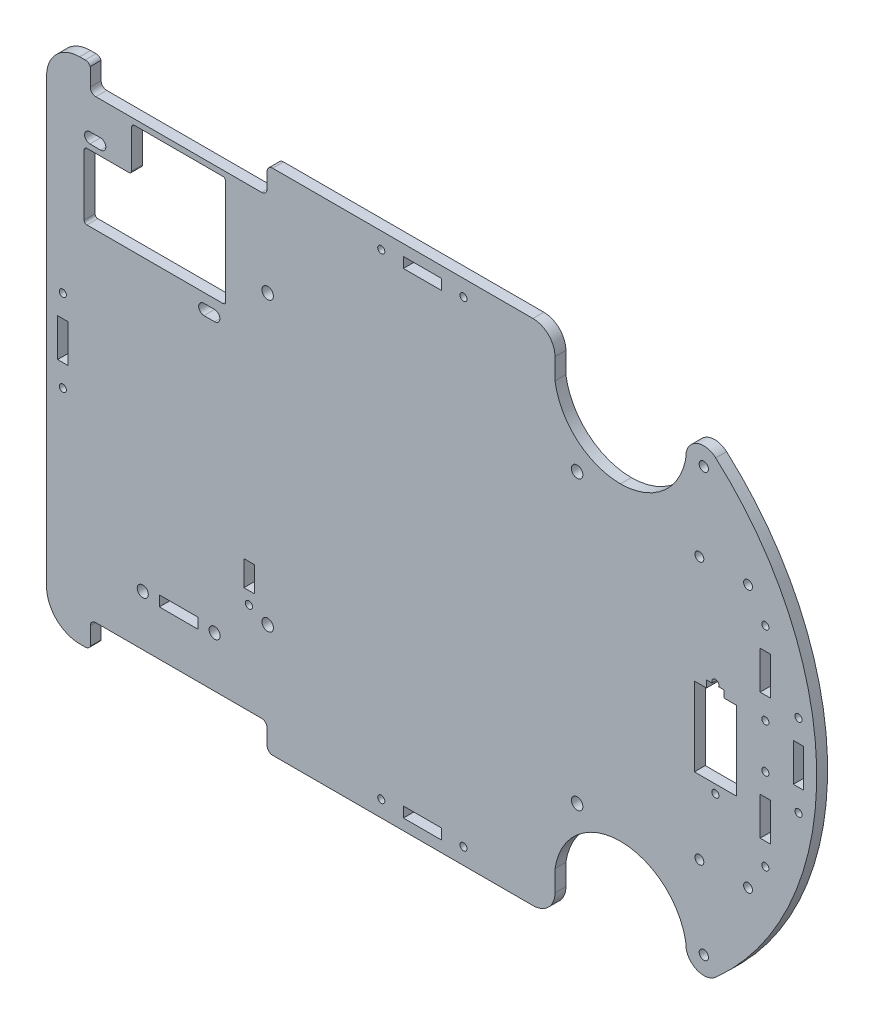
SolidWorks part; units mm, degrees
ref_plane "Alzado" through (0, 0, 0) normal (0, 0, 1) x (1, 0, 0)
ref_plane "Planta" through (0, 0, 0) normal (0, 1, 0) x (1, 0, 0)
ref_plane "Vista lateral" through (0, 0, 0) normal (1, 0, 0) x (0, 0, -1)
sketch "Croquis1" plane through (0, 0, 0) normal (0, 0, 1) x (1, 0, 0)
  line L1 (-107.95, -73.025) -> (107.95, -73.025)
  line L2 (-107.95, -73.025) -> (-107.95, 73.025)
  line L3 (-107.95, 73.025) -> (107.95, 73.025)
  line L4 (107.95, -73.025) -> (107.95, 73.025)
  line L5 (-107.95, -73.025) -> (107.95, 73.025) construction
  line L6 (-107.95, 73.025) -> (107.95, -73.025) construction
  point P0 (0, 0)
  dimension "D1" = 146.05
  dimension "D2" = 215.9
extrude "BI" add sketch "Croquis1" along normal blind 3.1242
sketch "Croquis2" plane through (0, 0, 3.1242) normal (0, 0, 1) x (1, 0, 0)
  line L0 (-107.95, -73.025) -> (107.95, -73.025) construction
  line L1 (107.95, 73.025) -> (43.634, 73.025)
  line L2 (107.95, 73.025) -> (107.95, -73.025)
  line L3 (107.95, -73.025) -> (43.634, -73.025)
  line L4 (43.634, 73.025) -> (43.634, -73.025)
  line L5 (0, 0) -> (107.95, 0) construction
  line L6 (71.3851, 73.025) -> (80.1989, 73.025)
  line L7 (71.3851, 73.025) -> (71.3851, 55.6514)
  line L8 (71.3851, 55.6514) -> (80.1989, 55.6514)
  line L9 (80.1989, 73.025) -> (80.1989, 55.6514)
  line L10 (80.1989, -73.025) -> (80.1989, -55.6514)
  line L11 (71.3851, -55.6514) -> (80.1989, -55.6514)
  line L12 (71.3851, -73.025) -> (71.3851, -55.6514)
  line L13 (71.3851, -73.025) -> (80.1989, -73.025)
  circle A0 centre (80.8339, 60.7314) radius 2.921
  circle A1 centre (80.8339, 60.7314) radius 1.3335
  circle A2 centre (80.8339, -60.7314) radius 1.3335
  circle A3 centre (80.8339, -60.7314) radius 2.921
  point P11 (75.792, 73.025)
  point P12 (75.792, 55.6514)
  point P13 (80.8339, 57.8104)
  point P14 (83.7549, 60.7314)
  point P28 (83.7549, -60.7314)
  point P29 (80.8339, -57.8104)
  point P30 (75.792, -55.6514)
  point P31 (75.792, -73.025)
  point P32 (80.8339, -59.3979)
  point P33 (80.8339, 59.3979)
  point P34 (80.8339, -62.0649)
  point P35 (80.8339, 62.0649)
  dimension "D3" = 5.842
  dimension "D4" = 1.5875
  dimension "D1" = 43.634
  dimension "D2" = 8.8138
  dimension "D5" = 3.556
  dimension "D6" = 17.3736
  dimension "D7" = 118.7958
  dimension "D8" = 118.7958
  dimension "D9" = 124.1298
extrude "Direccion" cut sketch "Croquis2" against normal through all contours L9 A1 | L9 A1 | A2 region at (81.0771, 60.7314, 3.1242) region at (79.9121, 60.7314, 3.1242)
sketch "Croquis9" plane through (0, 0, 3.1242) normal (0, 0, 1) x (1, 0, 0)
  line L0 (68.1339, 37.6809) -> (93.5339, 37.6809) construction
  line L1 (0, 0) -> (107.95, 0) construction
  line L2 (107.95, -73.025) -> (107.95, 73.025) construction
  line L3 (68.1339, -37.6809) -> (93.5339, -37.6809) construction
  circle A0 centre (68.1339, 37.6809) radius 1.27
  circle A1 centre (93.5339, 37.6809) radius 1.27
  circle A2 centre (93.5339, 37.6809) radius 2.794
  circle A3 centre (80.8339, 60.7314) radius 1.3335 construction
  circle A4 centre (80.8339, 60.7314) radius 1.3335
  circle A5 centre (93.5339, -37.6809) radius 1.27
  circle A6 centre (68.1339, -37.6809) radius 1.27
  circle A7 centre (80.8339, 37.6809) radius 1.27
  circle A8 centre (80.8339, -37.6809) radius 1.27
  circle A9 centre (79.5639, 37.6809) radius 1.27
  circle A10 centre (79.5639, -37.6809) radius 1.27
  point P4 (80.8339, 62.0649)
  point P5 (93.5339, 34.8869)
  point P9 (80.8339, 37.6809)
  point P22 (93.5339, -34.8869)
  point P23 (69.4039, 37.6809)
  point P24 (92.2639, 37.6809)
  dimension "D1" = 12.7
  dimension "D2" = 2.54
  dimension "D3" = 27.178
  dimension "D4" = 5.588
  dimension "D5" = 23.0505
  dimension "D6" = 2.667
extrude "Suspension" cut sketch "Croquis9" against normal through all contours A9 | A1 | A10 | A5
sketch "Croquis3" plane through (0, 0, 3.1242) normal (0, 0, 1) x (1, 0, 0)
  line L0 (107.95, -73.025) -> (107.95, 73.025) construction
  line L1 (107.95, 73.025) -> (-107.95, 73.025) construction
  line L2 (0, 0) -> (107.95, 0) construction
  line L3 (38.1, 73.025) -> (75.6745, 73.025)
  line L4 (38.1, 73.025) -> (38.1, 44.45)
  line L5 (38.1, 44.45) -> (75.6745, 44.45)
  line L6 (75.6745, 73.025) -> (75.6745, 44.45)
  line L7 (75.6745, -73.025) -> (75.6745, -44.45)
  line L8 (38.1, -44.45) -> (75.6745, -44.45)
  line L9 (38.1, -73.025) -> (38.1, -44.45)
  line L10 (38.1, -73.025) -> (75.6745, -73.025)
  line L11 (-107.95, -73.025) -> (107.95, -73.025) construction
  line L12 (-98.425, 73.025) -> (0, 73.025)
  line L13 (-107.95, 63.5) -> (-107.95, -63.5)
  line L14 (-98.425, -73.025) -> (0, -73.025)
  line L15 (0, 73.025) -> (0, -73.025)
  circle A0 centre (80.8339, 60.7314) radius 5.1594
  arc A1 (84.8004, 64.0308) -> (84.8004, -64.0308) centre (7.8219, 0) cw
  arc A2 (75.6745, 60.7314) -> (75.5727, 59.7195) centre (70.5945, 60.7314) cw
  arc A3 (31.75, 73.025) -> (38.1, 66.675) centre (31.75, 66.675) cw
  arc A4 (38.0482, 65.8655) -> (56.8873, 44.45) centre (56.8873, 63.4441) ccw
  arc A5 (38.0482, -65.8655) -> (56.8873, -44.45) centre (56.8873, -63.4441) cw
  arc A6 (31.75, -73.025) -> (38.1, -66.675) centre (31.75, -66.675) ccw
  arc A7 (75.5727, -59.7195) -> (56.8873, -44.45) centre (56.8873, -63.5176) ccw
  circle A8 centre (80.8339, -60.7314) radius 5.1594
  arc A9 (-107.95, -63.5) -> (-98.425, -73.025) centre (-98.425, -63.5) ccw
  arc A10 (-98.425, 73.025) -> (-107.95, 63.5) centre (-98.425, 63.5) ccw
  arc A11 (75.5727, 59.7195) -> (56.8873, 44.45) centre (56.8873, 63.5176) cw
  arc A12 (75.6745, -60.7314) -> (75.5727, -59.7195) centre (70.5945, -60.7314) ccw
  point P48 (-107.95, 73.025)
  line M6 (107.95, -73.025) -> (107.95, 73.025)
  line M7 (107.95, 73.025) -> (-107.95, 73.025)
  line M8 (-107.95, 73.025) -> (-107.95, -73.025)
  line M9 (-107.95, -73.025) -> (107.95, -73.025)
  dimension "D1" = 28.575
  dimension "D3" = 6.35
  dimension "D4" = 9.525
  dimension "D5" = 10.3187
  dimension "D6" = 5.08
  dimension "D2" = 38.1
extrude "Forma delantera" cut sketch "Croquis3" against normal through all contours A3 A4 L4 M7 | A11 A2 L6 L4 A4 M7 | A0 A1 L6 M6 M7 | A1 A8 L7 M9 M6 | L7 A12 A7 A5 L9 M9 | A6 L9 A5 M9 | A10 M7 M8 | A9 M8 M9 region at (56.8973, 60.3698, 3.1242) region at (36.6816, 71.6066, 3.1242) region at (97.7834, 56.0016, 3.1242) region at (97.7834, -56.0016, 3.1242) region at (-105.8224, 70.8974, 3.1242) region at (-105.8224, -70.8974, 3.1242) region at (36.6816, -71.6066, 3.1242) region at (56.8973, -60.3698, 3.1242)
sketch "Croquis5" plane through (0, 0, 3.1242) normal (0, 0, 1) x (1, 0, 0)
  line L0 (-98.425, -73.025) -> (31.75, -73.025) construction
  line L1 (-17.0815, -19.2786) -> (33.3375, -19.2786)
  line L2 (-17.0815, -19.2786) -> (-17.0815, -69.85)
  line L3 (-17.0815, -69.85) -> (33.3375, -69.85)
  line L4 (33.3375, -19.2786) -> (33.3375, -69.85)
  line L5 (-17.0815, -44.5643) -> (33.3375, -44.5643) construction
  line L6 (38.1, -66.675) -> (38.1, -60.6489) construction
  line L7 (33.3375, -69.85) -> (25.9715, -69.85)
  line L8 (33.3375, -69.85) -> (33.3375, -19.2786)
  line L9 (33.3375, -19.2786) -> (25.9715, -19.2786)
  line L10 (25.9715, -69.85) -> (25.9715, -19.2786)
  line L11 (-17.0815, -19.2786) -> (-6.9215, -19.2786)
  line L12 (-17.0815, -19.2786) -> (-17.0815, -69.85)
  line L13 (-17.0815, -69.85) -> (-6.9215, -69.85)
  line L14 (-6.9215, -19.2786) -> (-6.9215, -69.85)
  line L15 (25.9715, -33.2486) -> (33.3375, -33.2486)
  line L16 (25.9715, -33.2486) -> (25.9715, -55.88)
  line L17 (25.9715, -55.88) -> (33.3375, -55.88)
  line L18 (33.3375, -33.2486) -> (33.3375, -55.88)
  line L19 (-6.9215, -29.0576) -> (-17.0815, -29.0576)
  line L20 (-6.9215, -29.0576) -> (-6.9215, -60.071)
  line L21 (-6.9215, -60.071) -> (-17.0815, -60.071)
  line L22 (-17.0815, -29.0576) -> (-17.0815, -60.071)
  circle A0 centre (29.7815, -24.7396) radius 1.651
  circle A1 centre (-10.3505, -24.6126) radius 1.651
  circle A2 centre (29.7815, -64.389) radius 1.651
  circle A3 centre (-10.3505, -64.516) radius 1.651
  arc A4 (31.75, -55.88) -> (33.3375, -54.2925) centre (31.75, -54.2925) ccw
  arc A5 (29.6545, -55.88) -> (25.9715, -59.563) centre (29.6545, -59.563) ccw
  arc A6 (-12.0015, -60.071) -> (-17.0815, -54.991) centre (-12.0015, -54.991) cw
  arc A7 (-10.0965, -60.071) -> (-6.9215, -63.246) centre (-10.0965, -63.246) cw
  arc A8 (31.75, -33.2486) -> (33.3375, -34.8361) centre (31.75, -34.8361) cw
  arc A9 (29.6545, -33.2486) -> (25.9715, -29.5656) centre (29.6545, -29.5656) cw
  arc A10 (-12.0015, -29.0576) -> (-17.0815, -34.1376) centre (-12.0015, -34.1376) ccw
  arc A11 (-10.0965, -29.0576) -> (-6.9215, -25.8826) centre (-10.0965, -25.8826) ccw
  arc A12 (-6.9215, -20.0724) -> (-6.1278, -19.2786) centre (-6.1278, -20.0724) cw
  arc A13 (25.1777, -19.2786) -> (25.9715, -20.0724) centre (25.1777, -20.0724) cw
  arc A14 (25.1777, -69.85) -> (25.9715, -69.0563) centre (25.1777, -69.0563) ccw
  arc A15 (-6.9215, -69.0563) -> (-6.1278, -69.85) centre (-6.1278, -69.0563) ccw
  point P4 (31.4325, -24.7396)
  point P5 (29.7815, -23.0886)
  point P6 (-10.3505, -22.9616)
  point P14 (-12.0015, -24.6126)
  dimension "D5" = 3.302
  dimension "D16" = 1.5875
  dimension "D17" = 3.175
  dimension "D18" = 0.7937
  dimension "D1" = 50.5714
  dimension "D2" = 50.419
  dimension "D3" = 3.81
  dimension "D4" = 1.905
  dimension "D6" = 3.175
  dimension "D7" = 4.7625
  dimension "D8" = 5.08
  dimension "D9" = 3.683
  dimension "D10" = 7.366
  dimension "D11" = 10.16
  dimension "D12" = 13.97
  dimension "D13" = 13.97
  dimension "D14" = 9.779
  dimension "D15" = 9.779
extrude "Driver" [suppressed] cut sketch "Croquis5" against normal through all contours L22 L5 L14 L19 A10 | L5 L12 A6 L21 L20 | L14 L5 L16 L10 L1 | L16 L5 L18 A8 L15 | L5 L10 L17 A4 L8 | L5 L20 L14 L3 L10 | A5 L17 L10 | L21 A7 L14 | A11 L19 L14 | L15 A9 L10 | A1 | A3 | A2 | A0
sketch "Croquis6" [suppressed] plane through (0, 0, 3.1242) normal (0, 0, 1) x (1, 0, 0)
  line L0 (-33.45, 19.8814) -> (22.55, 19.8814)
  line L1 (-29.95, 48.8814) -> (19.05, 48.8814)
  line L2 (-29.95, 48.8814) -> (-29.95, -9.1186)
  line L3 (-29.95, -9.1186) -> (19.05, -9.1186)
  line L4 (19.05, 48.8814) -> (19.05, -9.1186)
  line L5 (-6.1278, -19.2786) -> (25.1777, -19.2786) construction
  line L6 (-5.45, -9.1186) -> (-5.45, 74.7014)
  line L7 (38.1, 66.675) -> (38.1, 60.6489) construction
  circle A0 centre (-29.95, 48.8814) radius 1.651
  circle A1 centre (19.05, 48.8814) radius 1.651
  circle A2 centre (19.05, -9.1186) radius 1.651
  circle A3 centre (-29.95, -9.1186) radius 1.651
  point P13 (-5.45, 19.8814)
  point P14 (19.05, 19.8814)
  point P16 (-5.45, 48.8814)
  point P19 (38.1, 63.662)
  dimension "D1" = 3.302
  dimension "D2" = 58
  dimension "D3" = 49
  dimension "D4" = 56
  dimension "D5" = 19.05
  dimension "D6" = 10.16
  dimension "D7" = 83.82
extrude "RasPi" [suppressed] cut sketch "Croquis6" against normal through all contours A3 | A2 | A1 | A0
sketch "Croquis8" plane through (0, 0, 3.1242) normal (0, 0, 1) x (1, 0, 0)
  line L0 (-93.98, 54.3306) -> (-61.214, 28.0162)
  line L1 (-62.738, 28.0162) -> (-59.69, 28.0162) construction
  line L7 (-62.738, 29.5402) -> (-59.69, 29.5402)
  line L11 (-62.738, 26.4922) -> (-59.69, 26.4922)
  line L12 (31.75, 73.025) -> (-98.425, 73.025) construction
  line L13 (-77.597, 66.3702) -> (-77.597, -66.3702) construction
  line L14 (-95.504, 54.3306) -> (-92.456, 54.3306) construction
  line L15 (-95.504, 55.8546) -> (-92.456, 55.8546)
  line L16 (-95.504, 52.8066) -> (-92.456, 52.8066)
  circle A0 centre (-93.98, 54.3306) radius 1.524
  circle A1 centre (-61.214, 28.0162) radius 1.524
  arc A2 (-62.738, 29.5402) -> (-62.738, 26.4922) centre (-62.738, 28.0162) ccw
  arc A3 (-59.69, 26.4922) -> (-59.69, 29.5402) centre (-59.69, 28.0162) ccw
  arc A4 (-95.504, 55.8546) -> (-95.504, 52.8066) centre (-95.504, 54.3306) ccw
  arc A5 (-92.456, 52.8066) -> (-92.456, 55.8546) centre (-92.456, 54.3306) ccw
  point P8 (-61.214, 26.4922)
  point P9 (-93.98, 52.8066)
  point P10 (-95.504, 54.3306)
  point P12 (-59.69, 28.0162)
  point P14 (-77.597, 0)
  point P16 (-61.214, 28.0162)
  point P22 (-93.98, 54.3306)
  point P30 (-77.597, 41.1734)
  dimension "D1" = 18.6944
  dimension "D3" = 3.048
  dimension "D4" = 3.048
  dimension "D2" = 32.766
  dimension "D5" = 77.597
  dimension "D6" = 45.0088
  dimension "D7" = 132.7404
extrude "Diferencial trasero" cut sketch "Croquis8" against normal through all contours A5 L15 A4 L16 | A3 L7 A2 L11
sketch "Croquis11" plane through (0, 0, 3.1242) normal (0, 0, 1) x (1, 0, 0)
  line L0 (-98.425, 73.025) -> (-95.25, 73.025)
  line L1 (-82.6984, 63.8302) -> (-57.2984, 63.8302)
  line L2 (-83.4921, 63.0365) -> (-83.4921, 32.2389)
  line L3 (-83.4921, 32.2389) -> (-57.2984, 32.2389)
  line L4 (-56.5046, 63.0365) -> (-56.5046, 33.0327)
  line L5 (-56.5046, 32.2389) -> (-96.3613, 32.2389)
  line L6 (-56.5046, 32.2389) -> (-56.5046, 51.2889)
  line L7 (-56.5046, 51.2889) -> (-96.3613, 51.2889)
  line L8 (-97.155, 33.0327) -> (-97.155, 50.4952)
  line L9 (-107.95, 63.5) -> (-107.95, -63.5) construction
  line L10 (31.75, 73.025) -> (-98.425, 73.025) construction
  line L11 (-95.25, 73.025) -> (-53.3296, 73.025)
  line L12 (-95.25, 73.025) -> (-95.25, 65.4177)
  line L13 (-95.25, 65.4177) -> (-53.3296, 65.4177)
  line L14 (-53.3296, 73.025) -> (-53.3296, 65.4177)
  line L15 (-43.0109, 73.025) -> (-44.5984, 73.025)
  line L16 (-95.3984, 80.6323) -> (-44.5984, 80.6323)
  line L17 (-95.3984, 80.6323) -> (-95.3984, 67.0052)
  line L18 (-93.8109, 65.4177) -> (-46.1859, 65.4177)
  line L19 (-44.5984, 80.6323) -> (-44.5984, 67.0052)
  line L20 (-95.3984, 80.6323) -> (-44.5984, 65.4177) construction
  line L21 (-95.3984, 65.4177) -> (-44.5984, 80.6323) construction
  line L22 (0, 0) -> (-107.95, 0) construction
  line L23 (-95.3984, -65.4177) -> (-44.5984, -80.6323) construction
  line L24 (-95.3984, -80.6323) -> (-44.5984, -65.4177) construction
  line L25 (-44.5984, -80.6323) -> (-44.5984, -67.0052)
  line L26 (-93.8109, -65.4177) -> (-46.1859, -65.4177)
  line L27 (-95.3984, -80.6323) -> (-95.3984, -67.0052)
  line L28 (-95.3984, -80.6323) -> (-44.5984, -80.6323)
  line L29 (-43.0109, -73.025) -> (-44.5984, -73.025)
  line L30 (-53.3296, -73.025) -> (-53.3296, -65.4177)
  line L31 (-95.25, -65.4177) -> (-53.3296, -65.4177)
  line L32 (-95.25, -73.025) -> (-95.25, -65.4177)
  line L33 (-95.25, -73.025) -> (-53.3296, -73.025)
  line L34 (-95.25, -73.025) -> (-95.25, -65.4177)
  line L35 (-98.425, -73.025) -> (-95.25, -73.025)
  line L36 (-62.738, 29.5402) -> (-59.69, 29.5402) construction
  circle A0 centre (-61.214, 28.0162) radius 1.27 construction
  arc A1 (-96.3613, 32.2389) -> (-97.155, 33.0327) centre (-96.3613, 33.0327) cw
  arc A2 (-96.3613, 51.2889) -> (-97.155, 50.4952) centre (-96.3613, 50.4952) ccw
  arc A3 (-57.2984, 32.2389) -> (-56.5046, 33.0327) centre (-57.2984, 33.0327) ccw
  arc A4 (-57.2984, 63.8302) -> (-56.5046, 63.0365) centre (-57.2984, 63.0365) cw
  arc A5 (-82.6984, 63.8302) -> (-83.4921, 63.0365) centre (-82.6984, 63.0365) ccw
  arc A6 (-83.4921, 52.0827) -> (-84.2859, 51.2889) centre (-84.2859, 52.0827) cw
  circle A7 centre (-93.98, 54.3306) radius 1.27 construction
  circle A8 centre (-93.98, 54.3306) radius 1.27
  arc A9 (-46.1859, 65.4177) -> (-44.5984, 67.0052) centre (-46.1859, 67.0052) ccw
  arc A10 (-95.3984, 67.0052) -> (-93.8109, 65.4177) centre (-93.8109, 67.0052) ccw
  arc A11 (-44.5984, 71.4375) -> (-43.0109, 73.025) centre (-43.0109, 71.4375) cw
  arc A12 (-95.25, 71.4375) -> (-96.8375, 73.025) centre (-96.8375, 71.4375) ccw
  arc A13 (-107.95, -63.5) -> (-98.425, -73.025) centre (-98.425, -63.5) ccw
  arc A14 (-107.95, 63.5) -> (-98.425, 73.025) centre (-98.425, 63.5) cw
  arc A15 (-95.25, -71.4375) -> (-96.8375, -73.025) centre (-96.8375, -71.4375) cw
  arc A17 (-44.5984, -71.4375) -> (-43.0109, -73.025) centre (-43.0109, -71.4375) ccw
  arc A18 (-95.3984, -67.0052) -> (-93.8109, -65.4177) centre (-93.8109, -67.0052) cw
  arc A19 (-46.1859, -65.4177) -> (-44.5984, -67.0052) centre (-46.1859, -67.0052) cw
  point P11 (-59.993, 28.3654)
  point P16 (-97.155, 32.2389)
  point P19 (-97.155, 51.2889)
  point P37 (-95.25, 54.3306)
  point P38 (-69.9984, 73.025)
  point P46 (-69.9984, 63.8302)
  point P91 (-69.9984, -73.025)
  point P92 (-59.69, 29.5402)
  dimension "D8" = 0.7937
  dimension "D9" = 1.5875
  dimension "D4" = 3.0417
  dimension "D11" = 50.8
  dimension "D12" = 1.5875
  dimension "D13" = 1.5875
  dimension "D2" = 3.175
  dimension "D3" = 10.4879
  dimension "D5" = 19.05
  dimension "D6" = 26.9875
  dimension "D7" = 9.4996
  dimension "D10" = 3.175
  dimension "D14" = 2.6987
extrude "Entrada transmision" cut sketch "Croquis11" against normal through all contours L1 A5 L2 L7 L4 A4 | L3 A3 L4 L7 L2 | L7 A2 L8 A1 L5 L2 | L2 A6 L7 | L17 A10 L18 L12 L11 L14 A9 L19 L16 | L14 L11 L12 L13 | L19 A11 L15 | L12 L17 A10 L18 | L17 | L27 | A18 L27 L32 L26 | L32 L33 L30 L26 | A19 L26 L30 L33 L27 L28 L25 | A17 L25 L29 | L32 A15 L27 L35 | A12 L12 L0 L17 region at (-95.7343, 72.7721, 3.1242) region at (-66.9396, 75.7248, 3.1242) region at (-95.3184, 72.4459, 3.1242) region at (-95.3242, 69.2214, 3.1242) region at (-74.2657, 69.2255, 3.1242) region at (-44.2438, 72.6704, 3.1242) region at (-69.9984, 57.5547, 3.1242) region at (-83.6694, 51.4662, 3.1242) region at (-70.0019, 41.7664, 3.1242) region at (-90.3167, 41.7639, 3.1242) region at (-66.9396, -75.7248, 3.1242) region at (-44.2438, -72.6704, 3.1242) region at (-95.7343, -72.7721, 3.1242) region at (-95.3184, -72.4459, 3.1242) region at (-95.3242, -69.2214, 3.1242) region at (-74.2657, -69.2255, 3.1242)
sketch "Croquis10" plane through (0, 0, 3.1242) normal (0, 0, 1) x (1, 0, 0)
  line L0 (-107.95, 63.5) -> (-107.95, -63.5) construction
  line L1 (61.3912, -19.4466) -> (51.7144, -19.4466)
  line L2 (61.3912, -19.4466) -> (61.3912, 12.2487)
  line L3 (61.3912, 12.2487) -> (51.7144, 12.2487)
  line L4 (51.7144, -19.4466) -> (51.7144, 12.2487)
  line L5 (61.3912, -19.4466) -> (51.7144, 12.2487) construction
  line L6 (61.3912, 12.2487) -> (51.7144, -19.4466) construction
  line L8 (67.5894, -6.0325) -> (90.1954, -6.0325)
  line L9 (67.5894, -6.0325) -> (67.5894, 6.0325)
  line L10 (67.5894, 6.0325) -> (90.1954, 6.0325)
  line L11 (90.1954, -6.0325) -> (90.1954, 6.0325)
  line L12 (67.5894, -6.0325) -> (90.1954, 6.0325) construction
  line L13 (67.5894, 6.0325) -> (90.1954, -6.0325) construction
  line L14 (90.1954, -6.0325) -> (90.1954, 6.0325)
  line L15 (90.1954, 3.1134) -> (90.1954, -1.9666)
  line L16 (90.1954, 6.0325) -> (78.1304, 6.0325)
  line L17 (90.1954, 6.0325) -> (90.1954, -16.5735)
  line L18 (90.1954, -2.54) -> (92.2274, -2.54)
  line L19 (90.1954, -2.54) -> (90.1954, 2.54)
  line L20 (90.1954, 2.54) -> (92.2274, 2.54)
  line L21 (92.2274, -2.54) -> (92.2274, 2.54)
  line L22 (90.1954, -16.5735) -> (78.1304, -16.5735)
  line L23 (78.1304, 6.0325) -> (78.1304, -16.5735)
  line L24 (81.6229, 6.0325) -> (86.7029, 6.0325)
  line L25 (81.6229, 6.0325) -> (81.6229, 8.0645)
  line L26 (81.6229, 8.0645) -> (86.7029, 8.0645)
  line L27 (86.7029, 6.0325) -> (86.7029, 8.0645)
  circle A3 centre (65.1637, 0) radius 1.016
  circle A4 centre (92.6211, 0) radius 1.016
  circle A5 centre (84.1629, 8.4607) radius 1.016
  circle A6 centre (84.1629, -19.0017) radius 1.016
  point P0 (56.5528, -3.599)
  point P16 (78.8924, 0)
  point P21 (90.1954, 0)
  point P26 (92.2274, 0)
  point P32 (84.1629, 8.0645)
  point P33 (84.1629, -16.5735)
  dimension "D5" = 2.4257
  dimension "D10" = 2.4282
  dimension "D2" = 2.032
  dimension "D1" = 159.6644
  dimension "D3" = 22.606
  dimension "D4" = 12.065
  dimension "D6" = 2.4257
  dimension "D7" = 175.5394
  dimension "D8" = 2.032
  dimension "D9" = 5.08
  dimension "D11" = 2.4282
extrude "Servo" cut sketch "Croquis10" against normal through all contours L8 L23 L22 L17 | L10 L23 L8 L11 L17 L14 L16 | A5 L26 L25 L16 L27 | L26 A5 | L26 A5 | A6 region at (84.1629, 0, 3.1242) region at (84.1629, -11.303, 3.1242) region at (84.1629, 6.9814, 3.1242) region at (84.1629, 8.6877, 3.1242) region at (84.1629, 7.8087, 3.1242) region at (84.1629, -19.0017, 3.1242)
sketch "Croquis12" plane through (0, 0, 3.1242) normal (0, 0, 1) x (1, 0, 0)
  line L1 (-44.45, -41.275) -> (44.45, -41.275)
  line L2 (-44.45, -41.275) -> (-44.45, 41.275)
  line L3 (-44.45, 41.275) -> (44.45, 41.275)
  line L4 (44.45, -41.275) -> (44.45, 41.275)
  line L5 (-44.45, -41.275) -> (44.45, 41.275) construction
  line L6 (-44.45, 41.275) -> (44.45, -41.275) construction
  circle A2 centre (44.45, 41.275) radius 1.651
  circle A3 centre (-44.45, 41.275) radius 1.651
  circle A4 centre (-44.45, -41.275) radius 1.651
  circle A5 centre (44.45, -41.275) radius 1.651
  point P0 (0, 0)
  dimension "D1" = 3.302
  dimension "D2" = 88.9
  dimension "D3" = 82.55
extrude "Soportes BS" cut sketch "Croquis12" against normal through all contours A3 | A2 | A5 | A4
sketch "Croquis7" plane through (0, 0, 3.1242) normal (0, 0, 1) x (1, 0, 0)
  line L0 (-93.8109, -65.4177) -> (-46.1859, -65.4177) construction
  line L1 (-75.5546, -49.3903) -> (-64.4421, -49.3903)
  line L2 (-75.5546, -49.3903) -> (-75.5546, -52.3875)
  line L3 (-75.5546, -52.3875) -> (-64.4421, -52.3875)
  line L4 (-64.4421, -49.3903) -> (-64.4421, -52.3875)
  line L9 (-98.425, -73.025) -> (-96.8375, -73.025) construction
  circle A0 centre (-59.6796, -50.8889) radius 1.5875
  circle A1 centre (-80.3171, -50.8889) radius 1.5875
  point P6 (-69.9984, -52.3875)
  point P7 (-69.9984, -65.4177)
  point P16 (-64.4421, -50.8889)
  dimension "D4" = 3.175
  dimension "D1" = 2.9972
  dimension "D2" = 11.1125
  dimension "D3" = 20.6375
  dimension "D5" = 4.7625
  dimension "D6" = 4.7625
extrude "Soporte eje" cut sketch "Croquis7" against normal through all contours A1 | A0 | L3 L4 L1 L2 region at (-59.6796, -50.8889, 3.1242) region at (-80.3171, -50.8889, 3.1242)
sketch "Croquis14" plane through (0, 0, 3.1242) normal (0, 0, 1) x (1, 0, 0)
  line L0 (-51.2659, -28.2194) -> (-48.2687, -28.2194)
  line L1 (-51.2659, -28.2194) -> (-51.2659, -35.4584)
  line L2 (-51.2659, -35.4584) -> (-48.2687, -35.4584)
  line L3 (-48.2687, -28.2194) -> (-48.2687, -35.4584)
  line L5 (-69.9984, -49.3903) -> (-69.9984, 32.2389) construction
  line L6 (-75.5546, -49.3903) -> (-64.4421, -49.3903) construction
  line L7 (-96.3613, 32.2389) -> (-57.2984, 32.2389) construction
  line L9 (-57.1079, -40.2495) -> (-82.8889, -40.2495)
  line L10 (-57.1079, -40.2495) -> (-57.1079, -30.6673)
  line L11 (-57.1079, -30.6673) -> (-82.8889, -30.6673)
  line L12 (-82.8889, -40.2495) -> (-82.8889, -30.6673)
  line L13 (-57.1079, -40.2495) -> (-82.8889, -30.6673) construction
  line L14 (-57.1079, -30.6673) -> (-82.8889, -40.2495) construction
  circle A0 centre (-49.8435, -39.0144) radius 1.016
  circle A1 centre (-59.6796, -50.8889) radius 1.5875 construction
  point P8 (-48.2687, -31.8389)
  point P17 (-69.9984, -35.4584)
  dimension "D3" = 2.032
  dimension "D6" = 19.05
  dimension "D1" = 2.9972
  dimension "D2" = 7.239
  dimension "D4" = 3.556
  dimension "D5" = 1.5748
  dimension "D7" = 5.842
  dimension "D8" = 25.781
extrude "Encoder" cut sketch "Croquis14" against normal through all contours L3 L2 L1 L0 | A0
sketch "Croquis15" plane through (0, 0, 3.1242) normal (0, 0, 1) x (1, 0, 0)
  arc A0 (84.8004, 64.0308) -> (84.8004, -64.0308) centre (7.8219, 0) cw
  arc A1 (84.2609, 64.5882) -> (84.2609, -64.5882) centre (26.8719, 0) cw
  arc A2 (84.8004, 64.0308) -> (75.6745, 60.7314) centre (80.8339, 60.7314) ccw construction
  arc A3 (75.6745, -60.7314) -> (84.8004, -64.0308) centre (80.8339, -60.7314) ccw construction
  arc A4 (84.8004, -64.0308) -> (84.8004, 64.0308) centre (7.8219, 0) ccw construction
  arc A5 (75.6745, -60.7314) -> (84.8004, -64.0308) centre (80.8339, -60.7314) ccw
  arc A6 (75.6745, 60.7314) -> (84.8004, 64.0308) centre (80.8339, 60.7314) cw
  dimension "D1" = 19.05
extrude "Saliente-Extruir1" add sketch "Croquis15" against normal up to surface (3.1242 mm away) contours A1 A6 A0 A5 region at (111.949, 0, 3.1242) up to face at (-48.8275, -39.0144, 0)
sketch "Croquis13" plane through (0, 0, 3.1242) normal (0, 0, 1) x (1, 0, 0)
  line L0 (0, 0) -> (107.95, 0) construction
  line L1 (0, -73.025) -> (0, 73.025) construction
  line L2 (106.5403, -5.461) -> (109.5375, -5.461)
  line L3 (106.5403, -5.461) -> (106.5403, 5.461)
  line L4 (106.5403, 5.461) -> (109.5375, 5.461)
  line L5 (109.5375, -5.461) -> (109.5375, 5.461)
  line L6 (106.5403, -5.461) -> (109.5375, 5.461) construction
  line L7 (106.5403, 5.461) -> (109.5375, -5.461) construction
  line L8 (31.75, 73.025) -> (-43.0109, 73.025) construction
  line L9 (-106.5403, 5.461) -> (-109.5375, -5.461) construction
  line L10 (-5.461, 66.8528) -> (5.461, 66.8528)
  line L11 (-5.461, 66.8528) -> (-5.461, 69.85)
  line L12 (-5.461, 69.85) -> (5.461, 69.85)
  line L13 (5.461, 66.8528) -> (5.461, 69.85)
  line L14 (-5.461, 66.8528) -> (5.461, 69.85) construction
  line L15 (-5.461, 69.85) -> (5.461, 66.8528) construction
  line L16 (-106.5403, -5.461) -> (-109.5375, 5.461) construction
  line L17 (-109.5375, -5.461) -> (-109.5375, 5.461)
  line L18 (-106.5403, 5.461) -> (-109.5375, 5.461)
  line L19 (-106.5403, -5.461) -> (-106.5403, 5.461)
  line L20 (-106.5403, -5.461) -> (-109.5375, -5.461)
  line L21 (-5.461, -69.85) -> (5.461, -66.8528) construction
  line L22 (-5.461, -66.8528) -> (5.461, -69.85) construction
  line L23 (5.461, -66.8528) -> (5.461, -69.85)
  line L24 (-5.461, -69.85) -> (5.461, -69.85)
  line L25 (-5.461, -66.8528) -> (-5.461, -69.85)
  line L26 (-5.461, -66.8528) -> (5.461, -66.8528)
  line L27 (97.0153, 12.7) -> (100.0125, 23.622) construction
  line L28 (100.0125, 12.7) -> (100.0125, 23.622)
  line L29 (97.0153, 12.7) -> (97.0153, 23.622)
  line L30 (97.0153, 23.622) -> (100.0125, 23.622)
  line L31 (97.0153, 23.622) -> (100.0125, 12.7) construction
  line L32 (97.0153, 12.7) -> (100.0125, 12.7)
  line L33 (97.0153, -23.622) -> (100.0125, -12.7) construction
  line L34 (97.0153, -12.7) -> (100.0125, -23.622) construction
  line L35 (97.0153, -12.7) -> (100.0125, -12.7)
  line L36 (97.0153, -23.622) -> (100.0125, -23.622)
  line L37 (97.0153, -12.7) -> (97.0153, -23.622)
  line L38 (100.0125, -12.7) -> (100.0125, -23.622)
  line L39 (-107.95, 63.5) -> (-107.95, -63.5) construction
  line L41 (-104.775, 5.461) -> (-101.7778, 5.461)
  line L42 (-104.775, 5.461) -> (-104.775, -5.461)
  line L43 (-104.775, -5.461) -> (-101.7778, -5.461)
  line L44 (-101.7778, 5.461) -> (-101.7778, -5.461)
  arc A0 (84.8004, -64.0308) -> (84.8004, 64.0308) centre (7.8219, 0) ccw construction
  circle A1 centre (108.0389, 11.811) radius 1.016
  circle A3 centre (108.0389, -11.811) radius 1.016
  circle A4 centre (11.811, 68.3514) radius 1.016
  circle A5 centre (-108.0389, 11.811) radius 1.016
  circle A6 centre (-108.0389, -11.811) radius 1.016
  circle A7 centre (-11.811, 68.3514) radius 1.016
  circle A8 centre (-11.811, -68.3514) radius 1.016
  circle A9 centre (11.811, -68.3514) radius 1.016
  circle A10 centre (98.5139, 29.972) radius 1.016
  circle A11 centre (98.5139, 6.35) radius 1.016
  circle A12 centre (98.5139, -6.35) radius 1.016
  circle A13 centre (98.5139, -29.972) radius 1.016
  circle A14 centre (-103.2764, 11.811) radius 1.016
  circle A15 centre (-103.2764, -11.811) radius 1.016
  point P6 (108.0389, 0)
  point P15 (0, 68.3514)
  point P25 (98.5139, 18.161)
  point P34 (-107.95, 0)
  point P46 (0, -68.3514)
  point P68 (98.5139, -18.161)
  point P70 (-98.3654, 0)
  point P75 (-103.2764, -5.461)
  point P76 (-86.7619, -5.461)
  point P80 (-101.7778, 0)
  dimension "D4" = 6.35
  dimension "D5" = 2.032
  dimension "D6" = 3.175
  dimension "D8" = 6.35
  dimension "D13" = 3.175
  dimension "D1" = 2.9972
  dimension "D2" = 10.922
  dimension "D3" = 1.5875
  dimension "D7" = 6.35
  dimension "D9" = 6.35
  dimension "D10" = 6.35
  dimension "D11" = 12.7
  dimension "D12" = 7.9375
extrude "Sensores de presencia" cut sketch "Croquis13" against normal through all contours L32 L28 L30 L29 | L35 L38 L36 L37 | A12 | A13 | A10 | A11 | A4 | L10 L13 L12 L11 | A7 | A9 | L24 L23 L26 L25 | A8 | A1 | L4 L5 L2 L3 | A3 | L43 L44 L41 L42 | A14 | A15
